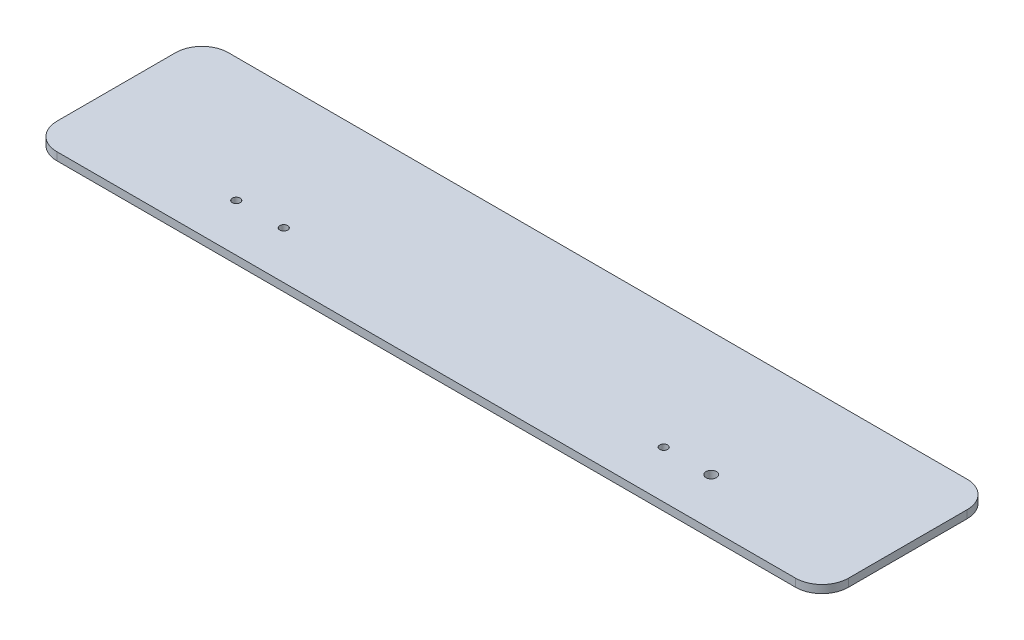
SolidWorks part; units mm, degrees
ref_plane "Front" through (0, 0, 0) normal (0, 0, 1) x (1, 0, 0)
ref_plane "Top" through (0, 0, 0) normal (0, 1, 0) x (1, 0, 0)
ref_plane "Right" through (0, 0, 0) normal (1, 0, 0) x (0, 0, -1)
sketch "草图1" plane through (0, 0, 0) normal (0, 1, 0) x (1, 0, 0)
  line L1 (0, 0) -> (300, 0)
  line L2 (0, 0) -> (0, 65)
  line L3 (0, 65) -> (300, 65)
  line L4 (300, 0) -> (300, 65)
  dimension "D1" = 300
  dimension "D2" = 65
extrude "凸台-拉伸1" add sketch "草图1" along normal blind 3
fillet "圆角1" radius 10 4 edges at (0, 1.5, 0) (0, 1.5, -65) (300, 1.5, 0) (300, 1.5, -65)
sketch "草图2" plane through (0, 3, 0) normal (0, 1, 0) x (1, 0, 0)
  line L0 (0, 18) -> (300, 18) construction
  line L1 (0, 55) -> (0, 10) construction
  line L2 (300, 10) -> (300, 55) construction
  line L3 (10, 0) -> (290, 0) construction
  circle A0 centre (60, 18) radius 1.5
  circle A1 centre (240, 18) radius 2
  circle A2 centre (78, 18) radius 1.5
  circle A3 centre (222, 18) radius 1.5
  dimension "D1" = 3
  dimension "D2" = 4
  dimension "D6" = 3
  dimension "D7" = 3
  dimension "D3" = 18
  dimension "D4" = 60
  dimension "D5" = 60
  dimension "D8" = 18
  dimension "D9" = 18
extrude "切除-拉伸1" cut sketch "草图2" against normal through all
